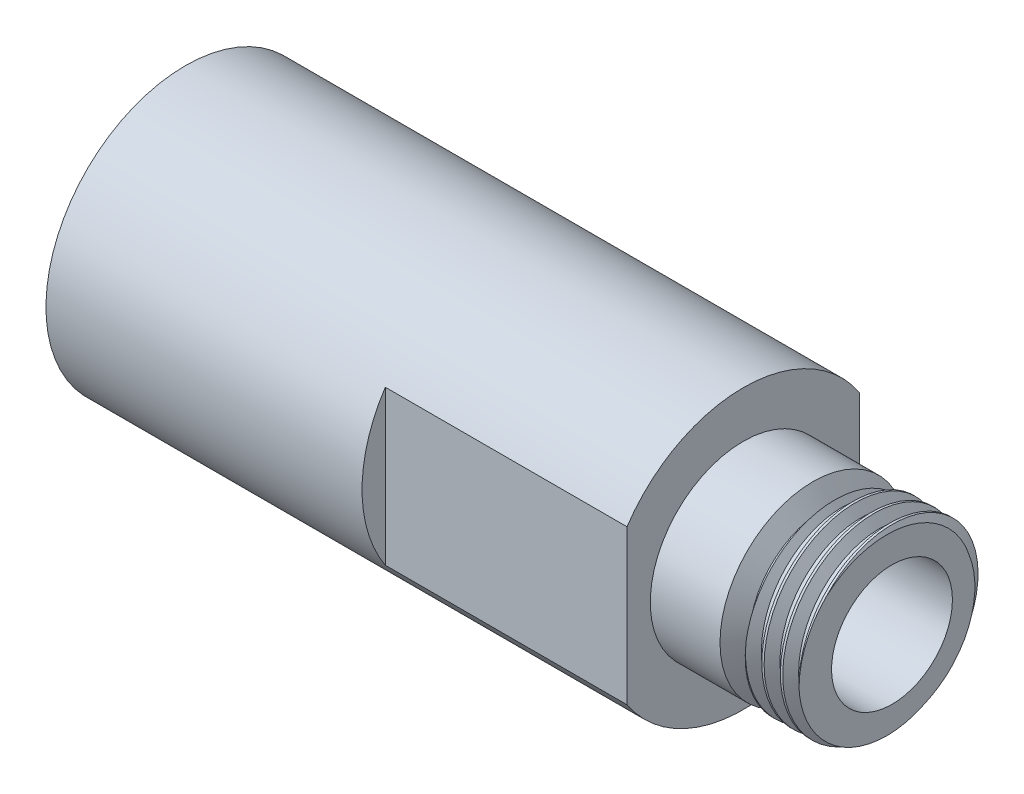
SolidWorks part; units mm, degrees
material "AISI Type 316L stainless steel"
ref_plane "Front Plane" through (0, 0, 0) normal (0, 0, 1) x (1, 0, 0)
ref_plane "Top Plane" through (0, 0, 0) normal (0, 1, 0) x (1, 0, 0)
ref_plane "Right Plane" through (0, 0, 0) normal (1, 0, 0) x (0, 0, -1)
sketch "Sketch1" plane through (0, 0, 0) normal (0, 0, 1) x (1, 0, 0)
  line L0 (0, 7.5) -> (40, 7.5)
  line L1 (40, 7.5) -> (40, 0)
  line L2 (40, 0) -> (0, 0)
  line L3 (0, 0) -> (0, 7.5)
  dimension "D1" = 7.5
  dimension "D2" = 40
revolve "Revolve1" add sketch "Sketch1" angle 360 about L2
sketch "Sketch4" plane through (40, 0, 0) normal (1, 0, 0) x (0, 0, -1)
  point P0 (0, 0)
hole_wizard "Ø6.5 (6.5) Diameter Hole1" positions "Sketch4" profile "Sketch5" hole size "Ø6.5" standard "DIN" end condition through all
sketch "Sketch5" plane through (40, 0, 0) normal (0, 1, 0) x (0, 0, -1)
  line L0 (0, 0) -> (0, 40)
  line L1 (0, 40) -> (3.25, 40)
  line L2 (3.25, 40) -> (3.25, 0.025)
  line L3 (3.25, 0.025) -> (3.275, 0)
  line L5 (3.275, 0) -> (0, 0)
  line L6 (-3.25, 0.025) -> (-3.275, 0) construction
  line L11 (0, -6.35) -> (0, 107.95) construction
  dimension "Thru Hole Dia." = 6.5
  dimension "Thru Hole Depth" = 40
  dimension "Near C'Sink Dia." = 6.55
  dimension "Near C'Sink Angle" = 90
sketch "Sketch7" plane through (40, 0, 0) normal (1, 0, 0) x (0, 0, -1)
  circle A0 centre (0, 0) radius 5
  circle A1 centre (0, 0) radius 7.5 construction
  circle A2 centre (0, 0) radius 7.5
  dimension "D1" = 10
extrude "Cut-Extrude2" cut sketch "Sketch7" against normal blind 10
sketch "Sketch6" plane through (30, 0, 0) normal (1, 0, 0) x (0, 0, -1)
  line L1 (-6.25, 4.1458) -> (6.25, 4.1458)
  line L2 (-6.25, 4.1458) -> (-6.25, -4.1458)
  line L3 (-6.25, -4.1458) -> (6.25, -4.1458)
  line L4 (6.25, 4.1458) -> (6.25, -4.1458)
  circle A0 centre (0, 0) radius 7.5 construction
  circle A1 centre (0, 0) radius 7.5
  dimension "D1" = 12.5
extrude "Cut-Extrude1" cut sketch "Sketch6" against normal blind 13 contours L2 | L4 region at (30, 0, 6.7538) region at (30, 0, -6.7538)
thread "Thread1" pitch 1 method cut profile "Thread Profile1" start angle 0, offset 3, length 8, pitch 1, diameter 10
ref_plane "Plane1" through (43, 0, 5) normal (0, -1, 0) x (0, 0, 1)
sketch "Thread Profile1" plane through (43, 0, 5) normal (0, -1, 0) x (0, 0, 1)
  line L0 (0, 0) -> (0, 1) construction
  line L11 (0, 0) -> (0, 0.875)
  line L12 (0, 0.875) -> (-0.5413, 0.5625)
  line L13 (-0.5413, 0.5625) -> (-0.5413, 0.3125)
  line L15 (-0.5413, 0.3125) -> (0, 0)
  line L17 (-0.5413, 0.4375) -> (0, 0.4375) construction
  point P2 (0, 0)
  dimension "Pitch" = 1
  dimension "Profile_Angle" = 60
  dimension "Profile_Land" = 0.25
  dimension "Profile_Height" = 0.5413
sketch "Sketch8" plane through (0, 0, 0) normal (0, 1, 0) x (1, 0, 0)
  line L0 (30, 5) -> (48.2889, 5)
  line L1 (33.75, 5) -> (34.3274, 4)
  line L2 (34.3274, 4) -> (34.5274, 4)
  line L3 (34.5274, 4) -> (35.1047, 5)
  line L4 (30, -6.25) -> (30, 6.25) construction
  line L5 (0, 0) -> (47.5249, 0) construction
  dimension "D1" = 60
  dimension "D2" = 60
  dimension "D3" = 0.2
  dimension "D4" = 1
  dimension "D5" = 3.75
revolve "Cut-Revolve1" cut sketch "Sketch8" angle 360 about L5 region at (34.4274, 0, -4.6238)
sketch "Sketch9" plane through (40, 0, 0) normal (1, 0, 0) x (0, 0, -1)
  circle A0 centre (0, 0) radius 5.3407
extrude "Cut-Extrude3" cut sketch "Sketch9" against normal blind 2
